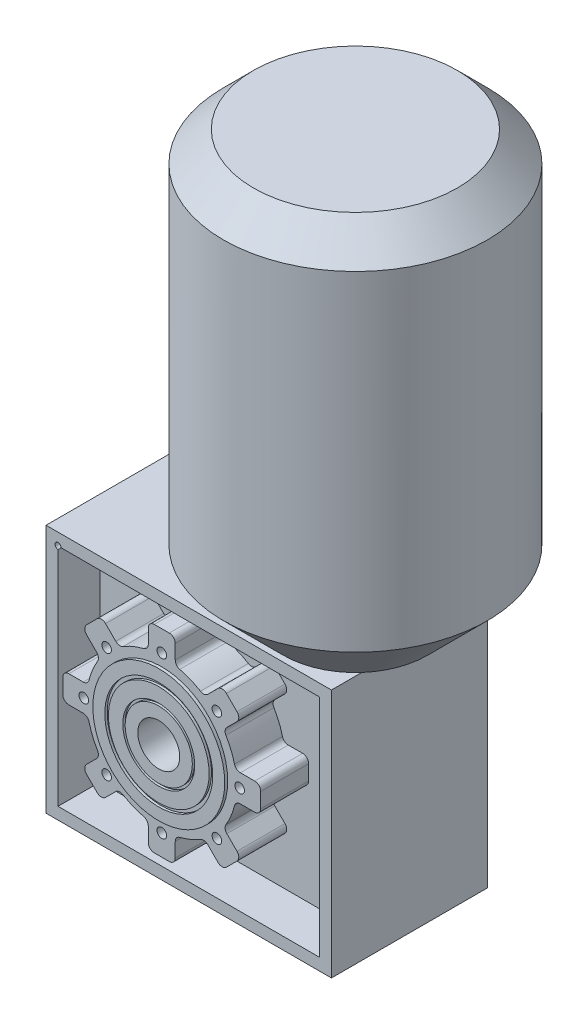
SolidWorks part; units mm, degrees
material "201 Annealed Stainless Steel (SS)"
ref_plane "Front Plane" through (0, 0, 0) normal (0, 0, 1) x (1, 0, 0)
ref_plane "Top Plane" through (0, 0, 0) normal (0, 1, 0) x (1, 0, 0)
ref_plane "Right Plane" through (0, 0, 0) normal (1, 0, 0) x (0, 0, -1)
sketch "Sketch1" plane through (0, 0, 0) normal (0, 0, 1) x (1, 0, 0)
  line L8 (35, 0) -> (273, 0)
  line L9 (273, 0) -> (273, 208)
  line L10 (273, 208) -> (35, 208)
  line L11 (35, 208) -> (35, 0)
  circle A1 centre (136.5, 104) radius 17.5
  circle A3 centre (45, 198) radius 2.5
  dimension "D1" = 101.5
  dimension "D2" = 104
  dimension "D6" = 35
  dimension "D3" = 238
  dimension "D4" = 208
  dimension "D5" = 35
extrude "Boss-Extrude1" add sketch "Sketch1" against normal blind 130
ref_plane "Plane1" through (0, 0, -65) normal (0, 0, 1) x (1, 0, 0)
sketch "Sketch3" plane through (0, 208, 0) normal (0, 1, 0) x (1, 0, 0)
  circle A1 centre (228, 65) radius 110
sketch "Sketch2" plane through (0, 0, -65) normal (0, 0, 1) x (1, 0, 0)
  line L0 (228, 157.8312) -> (228, 597.096) construction
  line L1 (288, 208) -> (338, 258)
  line L2 (338, 258) -> (338, 533)
  line L3 (338, 533) -> (313, 558)
  line L4 (313, 558) -> (228, 558)
  line L8 (228, 208) -> (288, 208)
  line L9 (228, 558) -> (228, 208)
revolve "Revolve1" add sketch "Sketch2" angle 360 about L0
sketch "Sketch4" plane through (0, 0, 0) normal (0, 0, 1) x (1, 0, 0)
  line L8 (263, 10) -> (263, 198)
  line L9 (45, 10) -> (263, 10)
  line L10 (45, 198) -> (45, 10)
  line L11 (263, 198) -> (45, 198)
  line L12 (263, 10) -> (263, 198)
  line L13 (45, 10) -> (263, 10)
  line L14 (45, 198) -> (45, 10)
  line L15 (263, 198) -> (45, 198)
  circle A0 centre (136.5, 104) radius 62.5
  circle A1 centre (136.5, 104) radius 17.5 construction
  dimension "D2" = 125
  dimension "D1" = 10
extrude "Cut-Extrude1" cut sketch "Sketch4" against normal blind 35
sketch "Sketch5" plane through (0, 0, -130) normal (0, 0, -1) x (-1, 0, 0)
  line L4 (-263, 198) -> (-263, 10)
  line L5 (-45, 198) -> (-263, 198)
  line L6 (-45, 10) -> (-45, 198)
  line L7 (-263, 10) -> (-45, 10)
  line L8 (-263, 198) -> (-263, 10)
  line L9 (-45, 198) -> (-263, 198)
  line L10 (-45, 10) -> (-45, 198)
  line L11 (-263, 10) -> (-45, 10)
  circle A1 centre (-136.5, 104) radius 62.5
  circle A2 centre (-136.5, 104) radius 62.5
  dimension "D1" = 0
  dimension "D2" = 0
extrude "Cut-Extrude2" cut sketch "Sketch5" against normal blind 46
sketch "Sketch6" plane through (0, 0, 0) normal (0, 0, 1) x (1, 0, 0)
  line L0 (136.5, 104) -> (136.5, 219.6781) construction
  line L1 (136.5, 104) -> (299.9938, 104) construction
  line L2 (125.25, 165.4792) -> (125.25, 186.5)
  line L3 (125.25, 186.5) -> (147.75, 186.5)
  line L4 (147.75, 165.4792) -> (147.75, 186.5)
  circle A0 centre (136.5, 169) radius 4 construction
  circle A1 centre (136.5, 39) radius 4 construction
  arc A2 (147.75, 165.4792) -> (125.25, 165.4792) centre (136.5, 104) ccw
  circle A3 centre (136.5, 104) radius 62.5 construction
  point P14 (136.5, 186.5)
  point P16 (147.75, 165.4792)
  point P17 (125.25, 165.4792)
  dimension "D1" = 8
  dimension "D2" = 122
  dimension "D4" = 20
  dimension "D3" = 22.5
extrude "Boss-Extrude2" add sketch "Sketch6" against normal up to surface (35 mm away) up to face at (199, 104, -35)
ref_axis "Axis1" through (136.5, 104, -130) along (0, 0, 1)
sketch "Sketch7" plane through (0, 0, 0) normal (0, 0, 1) x (1, 0, 0)
  circle A0 centre (136.5, 169) radius 4 construction
  circle A1 centre (136.5, 169) radius 4
extrude "Cut-Extrude3" cut sketch "Sketch7" against normal blind 20
fillet "Fillet1" radius 5 4 edges at (147.75, 186.5, -17.5) (147.75, 165.4792, -17.5) (125.25, 165.4792, -17.5) (125.25, 186.5, -17.5)
pattern_circular "CirPattern1" count 8 over 360 about axis through (136.5, 104, -130) along (0, 0, 1) of "Boss-Extrude2", "Cut-Extrude3", "Fillet1"
sketch "Sketch8" plane through (0, 0, 0) normal (0, 0, 1) x (1, 0, 0)
  line L24 (98.129, 158.2809) -> (89.6542, 166.7557)
  line L25 (82.5831, 166.7557) -> (73.7443, 157.9169)
  line L26 (73.7443, 150.8458) -> (82.2191, 142.371)
  line L27 (70.9852, 115.25) -> (59, 115.25)
  line L28 (54, 110.25) -> (54, 97.75)
  line L29 (59, 92.75) -> (70.9852, 92.75)
  line L30 (82.2191, 65.629) -> (73.7443, 57.1542)
  line L31 (73.7443, 50.0831) -> (82.5831, 41.2443)
  line L32 (89.6542, 41.2443) -> (98.129, 49.7191)
  line L33 (125.25, 38.4852) -> (125.25, 26.5)
  line L34 (130.25, 21.5) -> (142.75, 21.5)
  line L35 (147.75, 26.5) -> (147.75, 38.4852)
  line L36 (174.871, 49.7191) -> (183.3458, 41.2443)
  line L37 (190.4169, 41.2443) -> (199.2557, 50.0831)
  line L38 (199.2557, 57.1542) -> (190.7809, 65.629)
  line L39 (202.0148, 92.75) -> (214, 92.75)
  line L40 (219, 97.75) -> (219, 110.25)
  line L41 (214, 115.25) -> (202.0148, 115.25)
  line L42 (190.7809, 142.371) -> (199.2557, 150.8458)
  line L43 (199.2557, 157.9169) -> (190.4169, 166.7557)
  line L44 (183.3458, 166.7557) -> (174.871, 158.2809)
  line L45 (147.75, 169.5148) -> (147.75, 181.5)
  line L46 (142.75, 186.5) -> (130.25, 186.5)
  line L47 (125.25, 181.5) -> (125.25, 169.5148)
  line L48 (98.129, 158.2809) -> (89.6542, 166.7557)
  line L49 (82.5831, 166.7557) -> (73.7443, 157.9169)
  line L50 (73.7443, 150.8458) -> (82.2191, 142.371)
  line L51 (70.9852, 115.25) -> (59, 115.25)
  line L52 (54, 110.25) -> (54, 97.75)
  line L53 (59, 92.75) -> (70.9852, 92.75)
  line L54 (82.2191, 65.629) -> (73.7443, 57.1542)
  line L55 (73.7443, 50.0831) -> (82.5831, 41.2443)
  line L56 (89.6542, 41.2443) -> (98.129, 49.7191)
  line L57 (125.25, 38.4852) -> (125.25, 26.5)
  line L58 (130.25, 21.5) -> (142.75, 21.5)
  line L59 (147.75, 26.5) -> (147.75, 38.4852)
  line L60 (174.871, 49.7191) -> (183.3458, 41.2443)
  line L61 (190.4169, 41.2443) -> (199.2557, 50.0831)
  line L62 (199.2557, 57.1542) -> (190.7809, 65.629)
  line L63 (202.0148, 92.75) -> (214, 92.75)
  line L64 (219, 97.75) -> (219, 110.25)
  line L65 (214, 115.25) -> (202.0148, 115.25)
  line L66 (190.7809, 142.371) -> (199.2557, 150.8458)
  line L67 (199.2557, 157.9169) -> (190.4169, 166.7557)
  line L68 (183.3458, 166.7557) -> (174.871, 158.2809)
  line L69 (147.75, 169.5148) -> (147.75, 181.5)
  line L70 (142.75, 186.5) -> (130.25, 186.5)
  line L71 (125.25, 181.5) -> (125.25, 169.5148)
  circle A0 centre (182.4619, 58.0381) radius 4 construction
  circle A1 centre (136.5, 39) radius 4 construction
  circle A2 centre (90.5381, 58.0381) radius 4 construction
  circle A3 centre (71.5, 104) radius 4 construction
  circle A4 centre (201.5, 104) radius 4 construction
  circle A5 centre (182.4619, 149.9619) radius 4 construction
  circle A6 centre (136.5, 104) radius 17.5 construction
  circle A7 centre (90.5381, 149.9619) radius 4 construction
  arc A8 (199.2557, 150.8458) -> (199.2557, 157.9169) centre (195.7202, 154.3814) ccw
  arc A9 (199.2557, 150.8458) -> (199.2557, 157.9169) centre (195.7202, 154.3814) ccw
  arc A10 (190.4169, 166.7557) -> (183.3458, 166.7557) centre (186.8814, 163.2202) ccw
  arc A11 (190.4169, 166.7557) -> (183.3458, 166.7557) centre (186.8814, 163.2202) ccw
  arc A12 (168.7551, 157.5337) -> (174.871, 158.2809) centre (171.3355, 161.8164) ccw
  arc A13 (168.7551, 157.5337) -> (174.871, 158.2809) centre (171.3355, 161.8164) ccw
  arc A14 (168.7551, 157.5337) -> (151.5463, 164.6618) centre (136.5, 104) ccw
  arc A15 (168.7551, 157.5337) -> (151.5463, 164.6618) centre (136.5, 104) ccw
  circle A24 centre (136.5, 169) radius 4 construction
  circle A25 centre (182.4619, 58.0381) radius 4
  circle A26 centre (136.5, 39) radius 4
  circle A27 centre (90.5381, 58.0381) radius 4
  circle A28 centre (71.5, 104) radius 4
  circle A29 centre (201.5, 104) radius 4
  circle A30 centre (182.4619, 149.9619) radius 4
  circle A31 centre (136.5, 104) radius 17.5
  circle A32 centre (90.5381, 149.9619) radius 4
  circle A33 centre (136.5, 169) radius 4
  arc A74 (147.75, 169.5148) -> (151.5463, 164.6618) centre (152.75, 169.5148) ccw
  arc A75 (147.75, 169.5148) -> (151.5463, 164.6618) centre (152.75, 169.5148) ccw
  arc A76 (147.75, 181.5) -> (142.75, 186.5) centre (142.75, 181.5) ccw
  arc A77 (147.75, 181.5) -> (142.75, 186.5) centre (142.75, 181.5) ccw
  arc A78 (130.25, 186.5) -> (125.25, 181.5) centre (130.25, 181.5) ccw
  arc A79 (130.25, 186.5) -> (125.25, 181.5) centre (130.25, 181.5) ccw
  arc A80 (121.4537, 164.6618) -> (125.25, 169.5148) centre (120.25, 169.5148) ccw
  arc A81 (121.4537, 164.6618) -> (125.25, 169.5148) centre (120.25, 169.5148) ccw
  arc A82 (121.4537, 164.6618) -> (104.2449, 157.5337) centre (136.5, 104) ccw
  arc A83 (121.4537, 164.6618) -> (104.2449, 157.5337) centre (136.5, 104) ccw
  arc A84 (98.129, 158.2809) -> (104.2449, 157.5337) centre (101.6645, 161.8164) ccw
  arc A85 (98.129, 158.2809) -> (104.2449, 157.5337) centre (101.6645, 161.8164) ccw
  arc A86 (89.6542, 166.7557) -> (82.5831, 166.7557) centre (86.1186, 163.2202) ccw
  arc A87 (89.6542, 166.7557) -> (82.5831, 166.7557) centre (86.1186, 163.2202) ccw
  arc A88 (73.7443, 157.9169) -> (73.7443, 150.8458) centre (77.2798, 154.3814) ccw
  arc A89 (73.7443, 157.9169) -> (73.7443, 150.8458) centre (77.2798, 154.3814) ccw
  arc A90 (82.9663, 136.2551) -> (82.2191, 142.371) centre (78.6836, 138.8355) ccw
  arc A91 (82.9663, 136.2551) -> (82.2191, 142.371) centre (78.6836, 138.8355) ccw
  arc A92 (82.9663, 136.2551) -> (75.8382, 119.0463) centre (136.5, 104) ccw
  arc A93 (82.9663, 136.2551) -> (75.8382, 119.0463) centre (136.5, 104) ccw
  arc A94 (70.9852, 115.25) -> (75.8382, 119.0463) centre (70.9852, 120.25) ccw
  arc A95 (70.9852, 115.25) -> (75.8382, 119.0463) centre (70.9852, 120.25) ccw
  arc A96 (59, 115.25) -> (54, 110.25) centre (59, 110.25) ccw
  arc A97 (59, 115.25) -> (54, 110.25) centre (59, 110.25) ccw
  arc A98 (54, 97.75) -> (59, 92.75) centre (59, 97.75) ccw
  arc A99 (54, 97.75) -> (59, 92.75) centre (59, 97.75) ccw
  arc A100 (75.8382, 88.9537) -> (70.9852, 92.75) centre (70.9852, 87.75) ccw
  arc A101 (75.8382, 88.9537) -> (70.9852, 92.75) centre (70.9852, 87.75) ccw
  arc A102 (75.8382, 88.9537) -> (82.9663, 71.7449) centre (136.5, 104) ccw
  arc A103 (75.8382, 88.9537) -> (82.9663, 71.7449) centre (136.5, 104) ccw
  arc A104 (82.2191, 65.629) -> (82.9663, 71.7449) centre (78.6836, 69.1645) ccw
  arc A105 (82.2191, 65.629) -> (82.9663, 71.7449) centre (78.6836, 69.1645) ccw
  arc A106 (73.7443, 57.1542) -> (73.7443, 50.0831) centre (77.2798, 53.6186) ccw
  arc A107 (73.7443, 57.1542) -> (73.7443, 50.0831) centre (77.2798, 53.6186) ccw
  arc A108 (82.5831, 41.2443) -> (89.6542, 41.2443) centre (86.1186, 44.7798) ccw
  arc A109 (82.5831, 41.2443) -> (89.6542, 41.2443) centre (86.1186, 44.7798) ccw
  arc A110 (104.2449, 50.4663) -> (98.129, 49.7191) centre (101.6645, 46.1836) ccw
  arc A111 (104.2449, 50.4663) -> (98.129, 49.7191) centre (101.6645, 46.1836) ccw
  arc A112 (104.2449, 50.4663) -> (121.4537, 43.3382) centre (136.5, 104) ccw
  arc A113 (104.2449, 50.4663) -> (121.4537, 43.3382) centre (136.5, 104) ccw
  arc A114 (125.25, 38.4852) -> (121.4537, 43.3382) centre (120.25, 38.4852) ccw
  arc A115 (125.25, 38.4852) -> (121.4537, 43.3382) centre (120.25, 38.4852) ccw
  arc A116 (125.25, 26.5) -> (130.25, 21.5) centre (130.25, 26.5) ccw
  arc A117 (125.25, 26.5) -> (130.25, 21.5) centre (130.25, 26.5) ccw
  arc A118 (142.75, 21.5) -> (147.75, 26.5) centre (142.75, 26.5) ccw
  arc A119 (142.75, 21.5) -> (147.75, 26.5) centre (142.75, 26.5) ccw
  arc A120 (151.5463, 43.3382) -> (147.75, 38.4852) centre (152.75, 38.4852) ccw
  arc A121 (151.5463, 43.3382) -> (147.75, 38.4852) centre (152.75, 38.4852) ccw
  arc A122 (151.5463, 43.3382) -> (168.7551, 50.4663) centre (136.5, 104) ccw
  arc A123 (151.5463, 43.3382) -> (168.7551, 50.4663) centre (136.5, 104) ccw
  arc A124 (174.871, 49.7191) -> (168.7551, 50.4663) centre (171.3355, 46.1836) ccw
  arc A125 (174.871, 49.7191) -> (168.7551, 50.4663) centre (171.3355, 46.1836) ccw
  arc A126 (183.3458, 41.2443) -> (190.4169, 41.2443) centre (186.8814, 44.7798) ccw
  arc A127 (183.3458, 41.2443) -> (190.4169, 41.2443) centre (186.8814, 44.7798) ccw
  arc A128 (199.2557, 50.0831) -> (199.2557, 57.1542) centre (195.7202, 53.6186) ccw
  arc A129 (199.2557, 50.0831) -> (199.2557, 57.1542) centre (195.7202, 53.6186) ccw
  arc A130 (190.0337, 71.7449) -> (190.7809, 65.629) centre (194.3164, 69.1645) ccw
  arc A131 (190.0337, 71.7449) -> (190.7809, 65.629) centre (194.3164, 69.1645) ccw
  arc A132 (190.0337, 71.7449) -> (197.1618, 88.9537) centre (136.5, 104) ccw
  arc A133 (190.0337, 71.7449) -> (197.1618, 88.9537) centre (136.5, 104) ccw
  arc A134 (202.0148, 92.75) -> (197.1618, 88.9537) centre (202.0148, 87.75) ccw
  arc A135 (202.0148, 92.75) -> (197.1618, 88.9537) centre (202.0148, 87.75) ccw
  arc A136 (214, 92.75) -> (219, 97.75) centre (214, 97.75) ccw
  arc A137 (214, 92.75) -> (219, 97.75) centre (214, 97.75) ccw
  arc A138 (219, 110.25) -> (214, 115.25) centre (214, 110.25) ccw
  arc A139 (219, 110.25) -> (214, 115.25) centre (214, 110.25) ccw
  arc A140 (197.1618, 119.0463) -> (202.0148, 115.25) centre (202.0148, 120.25) ccw
  arc A141 (197.1618, 119.0463) -> (202.0148, 115.25) centre (202.0148, 120.25) ccw
  arc A142 (197.1618, 119.0463) -> (190.0337, 136.2551) centre (136.5, 104) ccw
  arc A143 (197.1618, 119.0463) -> (190.0337, 136.2551) centre (136.5, 104) ccw
  arc A144 (190.7809, 142.371) -> (190.0337, 136.2551) centre (194.3164, 138.8355) ccw
  arc A145 (190.7809, 142.371) -> (190.0337, 136.2551) centre (194.3164, 138.8355) ccw
  dimension "D1" = 0
extrude "Boss-Extrude3" add sketch "Sketch8" along normal blind 5
sketch "Sketch9" plane through (0, 0, 5) normal (0, 0, 1) x (1, 0, 0)
  circle A0 centre (136.5, 104) radius 55
  circle A1 centre (136.5, 104) radius 17.5 construction
  circle A2 centre (136.5, 104) radius 17.5
  dimension "D1" = 110
extrude "Boss-Extrude5" add sketch "Sketch9" along normal blind 2.5
sketch "Sketch10" plane through (0, 0, 7.5) normal (0, 0, 1) x (1, 0, 0)
  circle A0 centre (136.5, 104) radius 45
  circle A1 centre (136.5, 104) radius 42
  dimension "D1" = 90
  dimension "D2" = 84
extrude "Cut-Extrude4" cut sketch "Sketch10" against normal blind 2
sketch "Sketch11" plane through (0, 0, 7.5) normal (0, 0, 1) x (1, 0, 0)
  circle A0 centre (136.5, 104) radius 30
  circle A1 centre (136.5, 104) radius 17.5 construction
  circle A2 centre (136.5, 104) radius 28
  dimension "D1" = 60
  dimension "D2" = 2
extrude "Cut-Extrude5" cut sketch "Sketch11" against normal up to surface (2 mm away) up to face at (178.5, 104, 5.5)
